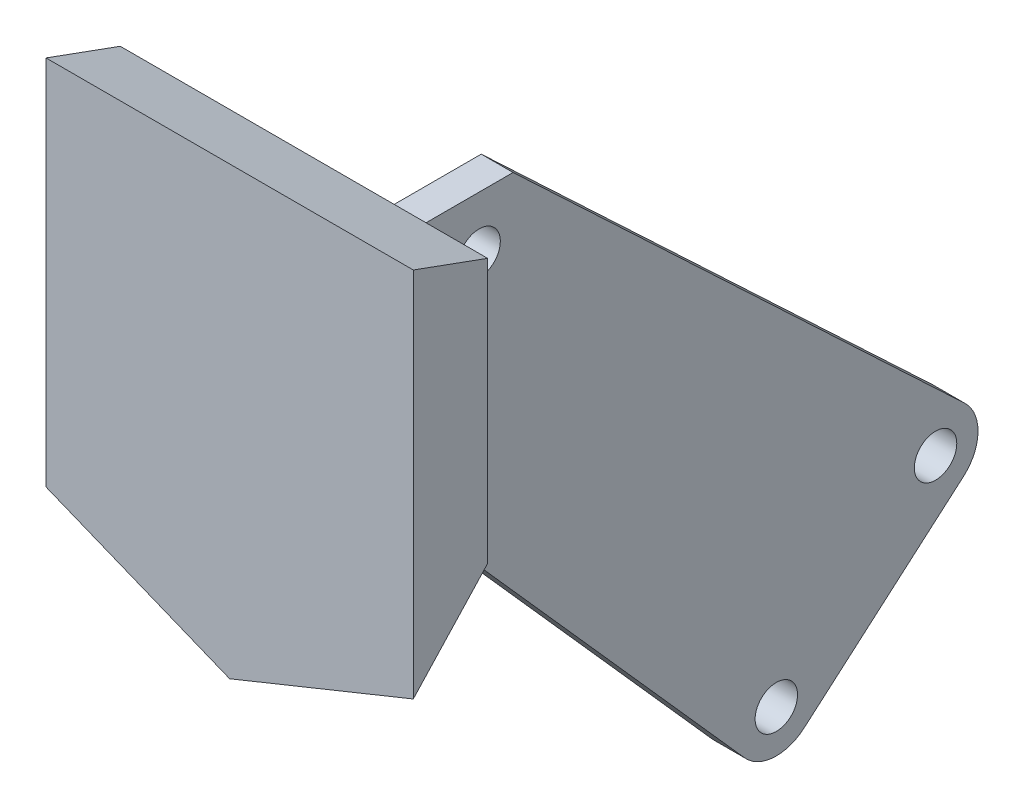
SolidWorks part; units mm, degrees
ref_plane "Plano frontal" through (0, 0, 0) normal (0, 0, 1) x (1, 0, 0)
ref_plane "Plano superior" through (0, 0, 0) normal (0, 1, 0) x (1, 0, 0)
ref_plane "Plano direito" through (0, 0, 0) normal (1, 0, 0) x (0, 0, -1)
sketch "Esboço10" plane through (0, 0, 0) normal (0, 0, 1) x (1, 0, 0)
  line L0 (-17.3, -17.5) -> (0, -24.5)
  line L3 (-17.3, 17.5) -> (17.3, 17.5)
  line L5 (0, -24.5) -> (17.3, -17.5)
  line L6 (-17.3, -17.5) -> (-17.3, 17.5)
  line L8 (17.3, 17.5) -> (17.3, -17.5)
  point P0 (0, 17.5)
  point P3 (17.3, 0)
  dimension "D1" = 7
  dimension "D2" = 35
  dimension "D3" = 34.6
extrude "Ressalto-extrusão4" add sketch "Esboço10" against normal blind 7
chamfer "Chanfro1" distance 7 angle 45 2 edges at (-8.65, -21, -7) (8.65, -21, -7)
chamfer "Chanfro2" distance 7 angle 20 1 edges at (0, 17.5, -7)
sketch "Esboço12" plane through (0, 0, 0) normal (0, 1, 0) x (1, 0, 0)
  line L0 (-17.3, 7) -> (-23.5, 13.2)
  line L1 (-23.5, 13.2) -> (-23.5, 15.2)
  line L2 (-23.5, 15.2) -> (8.5, 15.2)
  line L3 (8.5, 15.2) -> (8.5, 7)
  line L4 (-17.3, 7) -> (17.3, 7) construction
  line L5 (8.5, 7) -> (-17.3, 7)
  line L6 (0, 0) -> (0, 9.4279) construction
  line L7 (17.3, 0) -> (-17.3, 0) construction
  dimension "D1" = 32
  dimension "D2" = 47
  dimension "D3" = 45
  dimension "D4" = 2
extrude "Ressalto-extrusão5" add sketch "Esboço12" against normal blind 12
sketch "Esboço13" plane through (0, 0, -15.2) normal (0, 0, -1) x (-1, 0, 0)
  line L0 (7.5, 0) -> (7.5, -12) construction
  line L1 (-8.5, 0) -> (23.5, 0) construction
  line L2 (-8.5, -12) -> (23.5, -12) construction
  line L3 (-8.5, 0) -> (23.5, 0) construction
  circle A0 centre (0.5, -7.3979) radius 2
  circle A1 centre (-5, -5) radius 2
  circle A2 centre (20, -5) radius 2
  circle A3 centre (14.5, -7.3979) radius 2
  point P10 (0, 0)
  dimension "D4" = 4
  dimension "D5" = 5
  dimension "D1" = 14
  dimension "D2" = 25
  dimension "D3" = 6
extrude "Corte-extrusão1" cut sketch "Esboço13" against normal blind 5
sketch "Esboço14" plane through (8.5, 0, 0) normal (1, 0, 0) x (0, 0, -1)
  line L1 (57.7432, -25.1366) -> (15.2, 14.9522)
  line L2 (15.2, 14.9522) -> (7, 14.9522)
  line L3 (7, 14.9522) -> (7, -9.9487)
  line L4 (57.6197, -31.0705) -> (42.6197, -44.0705)
  line L5 (37.0106, -43.7055) -> (7, -9.9487)
  line L6 (15.2, 0) -> (15.2, -12) construction
  circle A0 centre (12, 9.9522) radius 2
  circle A1 centre (55, -28.0478) radius 2
  arc A2 (57.6197, -31.0705) -> (57.7432, -25.1366) centre (55, -28.0478) ccw
  arc A3 (42.6197, -44.0705) -> (37.0106, -43.7055) centre (40, -41.0478) cw
  circle A4 centre (40, -41.0478) radius 2
  point P5 (36.8504, -43.4275)
  point P6 (13.832, 10.0551)
  point P19 (7, 13.9459)
  point P21 (0, 0)
  dimension "D3" = 4
  dimension "D4" = 8
  dimension "D1" = 43
  dimension "D2" = 38
  dimension "D6" = 5
  dimension "D7" = 13
  dimension "D8" = 15
  dimension "D9" = 5
extrude "Ressalto-extrusão6" add sketch "Esboço14" along normal blind 3
